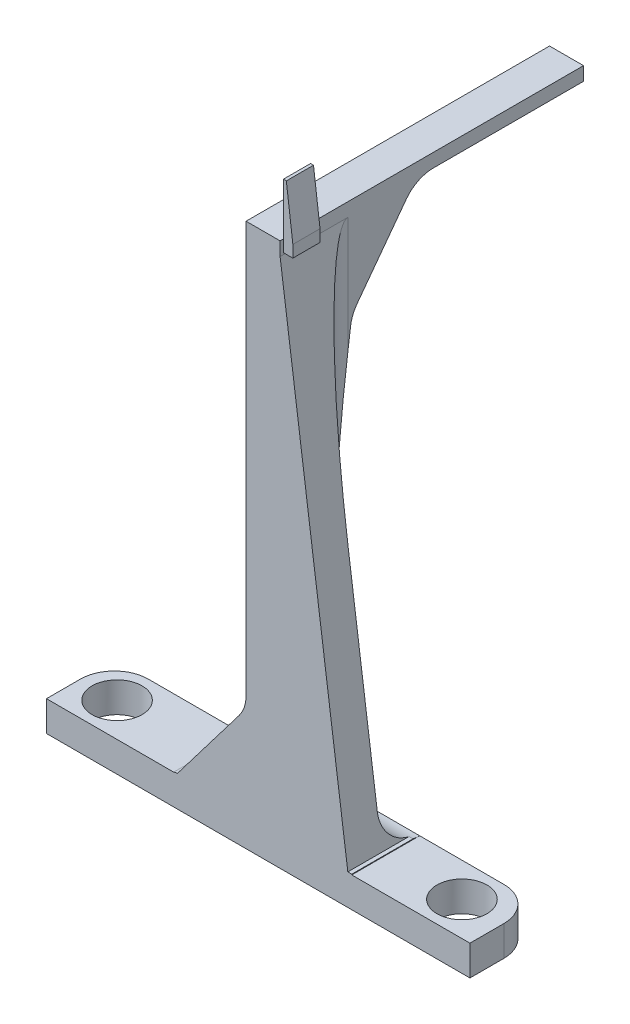
SolidWorks part; units mm, degrees
ref_plane "Front Plane" through (0, 0, 0) normal (0, 0, 1) x (1, 0, 0)
ref_plane "Top Plane" through (0, 0, 0) normal (0, 1, 0) x (1, 0, 0)
ref_plane "Right Plane" through (0, 0, 0) normal (1, 0, 0) x (0, 0, -1)
sketch "Sketch3" plane through (0, 0, 0) normal (0, 1, 0) x (1, 0, 0)
  line L5 (82.2662, 0.2065) -> (77.2564, 0.2065)
  line L6 (77.2564, 0.2065) -> (77.2564, -44.4916)
  line L7 (77.2564, -44.4916) -> (82.2662, -44.4916)
  line L8 (82.2662, -44.4916) -> (82.2662, 0.2065)
sketch "Sketch4" plane through (0, 0, 0) normal (0, 0, 1) x (1, 0, 0)
  line L0 (82.2662, 7.62) -> (82.6964, 7.62)
  line L1 (82.6964, 7.62) -> (83.6578, 0)
  line L2 (83.6578, 0) -> (83.6578, -1.7566)
  line L3 (83.6578, -1.7566) -> (77.2026, -1.7566)
  line L4 (77.2026, -1.7566) -> (77.2564, 0)
  line L5 (77.2564, 0) -> (82.2662, 0)
  line L6 (82.2662, 0) -> (82.2662, 7.62)
extrude "Boss-Extrude3" add sketch "Sketch4" along normal blind 4 from offset 40
extrude "Boss-Extrude4" add sketch "Sketch3" against normal blind 2
sketch "Sketch5" plane through (0, 0, 0) normal (0, 0, 1) x (1, 0, 0)
  circle A0 centre (6.8787, 52) radius 75 construction
  dimension "D1" = 52
sketch "Sketch6" plane through (0, 0, 44.4916) normal (0, 0, 1) x (1, 0, 0)
  line L0 (77.2564, -2) -> (77.2564, -3.0404)
  line L1 (77.2564, -3.0404) -> (77.2564, -62.2131)
  line L2 (77.2564, -62.2131) -> (67.1373, -75.5092)
  line L3 (67.1373, -75.5092) -> (66.6971, -75.5092)
  line L4 (66.6971, -75.5092) -> (66.6971, -80.0524)
  line L5 (66.6971, -80.0524) -> (92.8263, -80.0524)
  line L6 (92.8263, -80.0524) -> (92.8263, -75.5092)
  line L7 (92.8263, -75.5092) -> (92.2446, -75.5092)
  line L8 (92.2446, -75.5092) -> (82.2662, -2)
  line L9 (82.2662, -2) -> (77.2564, -2)
extrude "Boss-Extrude5" add sketch "Sketch6" against normal blind 5
sketch "Sketch7" plane through (0, 0, 44.4916) normal (0, 0, 1) x (1, 0, 0)
  line L1 (110.2307, -80.0524) -> (47.8566, -80.0524)
  line L2 (110.2307, -80.0524) -> (110.2307, -75.6081)
  line L3 (110.2307, -75.6081) -> (47.8566, -75.6081)
  line L4 (47.8566, -80.0524) -> (47.8566, -75.6081)
extrude "Boss-Extrude6" add sketch "Sketch7" against normal blind 10
sketch "Sketch8" plane through (0, -75.6081, 0) normal (0, 1, 0) x (1, 0, 0)
  circle A0 centre (53.2537, -39.4916) radius 3.68
  circle A1 centre (104.0537, -39.4916) radius 3.68
  dimension "D1" = 2
extrude "Cut-Extrude1" cut sketch "Sketch8" against normal blind 10
sketch "Sketch9" plane through (82.2662, 0, 0) normal (1, 0, 0) x (0, 0, -1)
  line L0 (-24.4295, -2) -> (-33.921, -14.7259)
  line L1 (-33.921, -14.7259) -> (-39.4916, -56.5494)
  line L2 (-39.4916, -56.5494) -> (-39.4916, -2)
  line L3 (-39.4916, -2) -> (-24.4295, -2)
extrude "Boss-Extrude7" add sketch "Sketch9" against normal blind 2
fillet "Fillet1" radius 5 8 edges at (81.2662, -2, 24.4295) (81.2662, -14.7259, 33.921) (80.2662, -29.2747, 39.4916) (77.2564, -62.2131, 41.9916) (79.7617, -75.6081, 39.4916) (47.8566, -77.8302, 34.4916) (110.2307, -77.8302, 34.4916)
